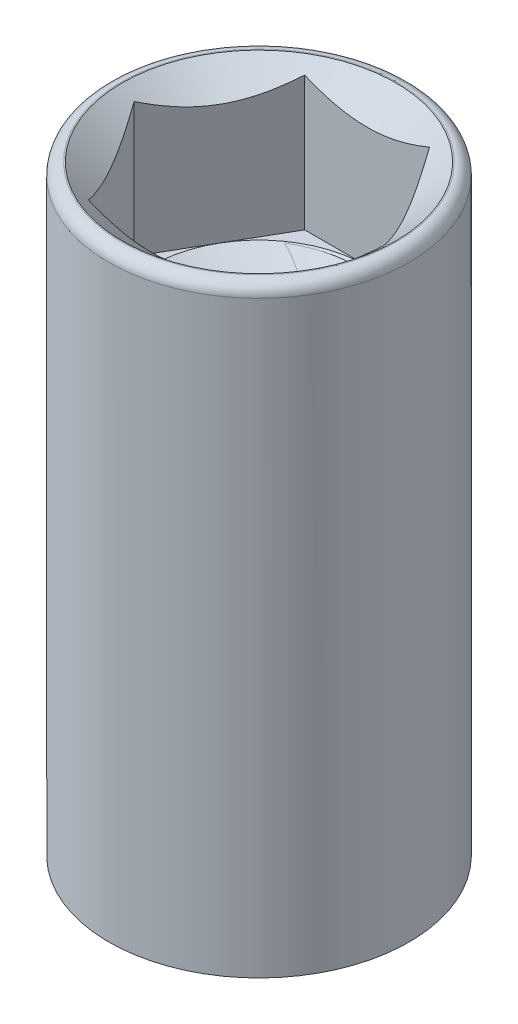
SolidWorks part; units mm, degrees
ref_plane "Alzado" through (0, 0, 0) normal (0, 0, 1) x (1, 0, 0)
ref_plane "Planta" through (0, 0, 0) normal (0, 1, 0) x (1, 0, 0)
ref_plane "Vista lateral" through (0, 0, 0) normal (1, 0, 0) x (0, 0, -1)
sketch "Croquis1" plane through (0, 0, 0) normal (0, 0, 1) x (1, 0, 0)
  line L0 (0, -8.5981) -> (0, -90.1857) construction
  line L1 (5.7, 0) -> (6.25, 0)
  line L2 (6.25, 0) -> (6.25, -25)
  line L3 (3.375, -25) -> (6.25, -25)
  line L5 (3.375, -6.6495) -> (3.375, -25)
  line L7 (4.5, -1) -> (4.5, -6)
  line L8 (4.5, -6) -> (3.375, -6.6495)
  line L9 (0, 0) -> (0, -117.5457) construction
  line L10 (4.5, -1) -> (5.7, 0)
  point P10 (4.5, 0)
  dimension "D2" = 25
  dimension "D3" = 6.75
  dimension "D5" = 9
  dimension "D6" = 6
  dimension "D7" = 60
  dimension "D10" = 1.2
revolve "Revolución1" add sketch "Croquis1" angle 360 about L0
fillet "Redondeo1" radius 0.5 1 edges at (-6.25, 0, 0)
sketch "Croquis2" plane through (0, 0, 0) normal (0, 1, 0) x (1, 0, 0)
  line L1 (5.1962, 0) -> (2.5981, 4.5)
  line L2 (2.5981, 4.5) -> (-2.5981, 4.5)
  line L3 (-2.5981, 4.5) -> (-5.1962, 0)
  line L4 (-5.1962, 0) -> (-2.5981, -4.5)
  line L5 (-2.5981, -4.5) -> (2.5981, -4.5)
  line L6 (2.5981, -4.5) -> (5.1962, 0)
  circle A0 centre (0, 0) radius 4.5 construction
  dimension "D1" = 9
extrude "Cortar-Extruir1" cut sketch "Croquis2" against normal blind 6
ref_plane "Plano1" through (0, -35, 0) normal (0, -1, 0) x (-1, 0, 0)
sketch "Croquis3" plane through (0, -35, 0) normal (0, -1, 0) x (-1, 0, 0)
  circle A0 centre (0, 0) radius 3.375 construction
  circle A1 centre (0, 0) radius 3.375
curve "Hélice/Espiral1" pitch 1.25 height 45 radius 3.375 centre (0, -35, 0) axis (0, 1, 0) start towards (-0.7071, 0, 0.7071)
ref_plane "Plano2" through (-2.3865, -35, 2.3865) normal (0.7059, 0.0588, 0.7059) x (0.7083, -0.0586, -0.7034)
sketch "Croquis4" plane through (-2.3865, -35, 2.3865) normal (0.7059, 0.0588, 0.7059) x (0.7083, -0.0586, -0.7034)
  line L0 (-0.0212, -0.0026) -> (-0.0798, 1.2274)
  line L1 (-0.0798, 1.2274) -> (-1.1106, 0.5041)
  line L2 (-1.1106, 0.5041) -> (-0.0212, -0.0026)
  point P2 (0, 0)
  point P4 (-1.2443, 0.5663)
  point P5 (-0.0798, 1.2274)
  dimension "D1" = 60
sweep "Cortar-Barrer1" cut profiles "Croquis4" path "Hélice/Espiral1" align with end faces yes
